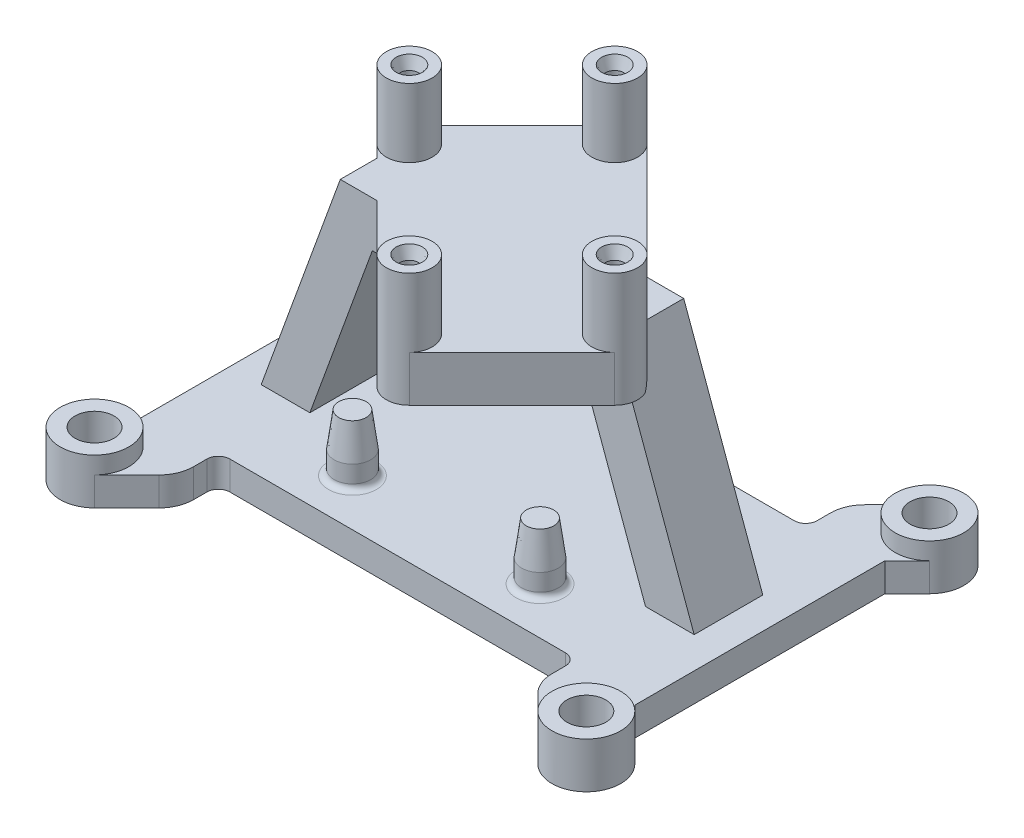
SolidWorks part; units mm, degrees
ref_plane "Front Plane" through (0, 0, 0) normal (0, 0, 1) x (1, 0, 0)
ref_plane "Top Plane" through (0, 0, 0) normal (0, 1, 0) x (1, 0, 0)
ref_plane "Right Plane" through (0, 0, 0) normal (1, 0, 0) x (0, 0, -1)
sketch "Sketch1" plane through (0, 0, 0) normal (0, 1, 0) x (1, 0, 0)
  line L1 (-21.5, 15) -> (21.5, 15) construction
  line L2 (-21.5, 15) -> (-21.5, -15) construction
  line L3 (-21.5, -15) -> (21.5, -15) construction
  line L4 (21.5, 15) -> (21.5, -15) construction
  line L5 (-21.5, 15) -> (21.5, -15) construction
  line L6 (-21.5, -15) -> (21.5, 15) construction
  circle A0 centre (-21.5, 15) radius 1.7
  circle A1 centre (21.5, 15) radius 1.7
  circle A2 centre (21.5, -15) radius 1.7
  circle A3 centre (-21.5, -15) radius 1.7
  circle A4 centre (-21.5, 15) radius 3
  circle A5 centre (-21.5, -15) radius 3
  circle A6 centre (21.5, -15) radius 3
  circle A7 centre (21.5, 15) radius 3
  point P0 (0, 0)
  dimension "D3" = 3.4
  dimension "D4" = 6
  dimension "D1" = 43
  dimension "D2" = 30
extrude "Boss-Extrude1" add sketch "Sketch1" along normal blind 4
sketch "Sketch2" plane through (0, 0, 0) normal (0, 1, 0) x (1, 0, 0)
  line L0 (-21.5, 15) -> (-18.6716, 12.1716) construction
  line L1 (-19.3787, 17.1213) -> (-16.5503, 14.2929)
  line L2 (-23.6213, 12.8787) -> (-21.6716, 10.9289)
  line L3 (-21.5, -15) -> (-18.6716, -12.1716) construction
  line L4 (-23.6213, -12.8787) -> (-21.6716, -10.9289)
  line L5 (-19.3787, -17.1213) -> (-16.5503, -14.2929)
  line L6 (-18.6716, 12.1716) -> (-18.6716, -12.1716) construction
  line L7 (-15.6716, 12.1716) -> (-15.6716, -12.1716)
  line L8 (-21.6716, 10.9289) -> (-21.6716, -10.9289)
  line L9 (0, -1000) -> (0, 49000) construction
  line L10 (18.6716, 12.1716) -> (18.6716, -12.1716) construction
  line L11 (21.5, -15) -> (18.6716, -12.1716) construction
  line L12 (21.5, 15) -> (18.6716, 12.1716) construction
  line L13 (21.6716, 10.9289) -> (21.6716, -10.9289)
  line L14 (15.6716, 12.1716) -> (15.6716, -12.1716)
  line L15 (19.3787, -17.1213) -> (16.5503, -14.2929)
  line L16 (23.6213, -12.8787) -> (21.6716, -10.9289)
  line L17 (23.6213, 12.8787) -> (21.6716, 10.9289)
  line L18 (19.3787, 17.1213) -> (16.5503, 14.2929)
  arc A0 (-19.3787, 17.1213) -> (-23.6213, 12.8787) centre (-21.5, 15) ccw
  circle A2 centre (-21.5, 15) radius 3 construction
  arc A3 (-23.6213, -12.8787) -> (-19.3787, -17.1213) centre (-21.5, -15) ccw
  arc A4 (-16.5503, -14.2929) -> (-15.6716, -12.1716) centre (-18.6716, -12.1716) ccw
  circle A5 centre (-21.5, -15) radius 3 construction
  arc A6 (-15.6716, 12.1716) -> (-16.5503, 14.2929) centre (-18.6716, 12.1716) ccw
  arc A7 (-16.5503, -14.2929) -> (-15.6716, -12.1716) centre (-18.6716, -12.1716) ccw
  arc A8 (-15.6716, 12.1716) -> (-16.5503, 14.2929) centre (-18.6716, 12.1716) ccw
  arc A9 (15.6716, 12.1716) -> (16.5503, 14.2929) centre (18.6716, 12.1716) cw
  arc A10 (16.5503, -14.2929) -> (15.6716, -12.1716) centre (18.6716, -12.1716) cw
  arc A11 (15.6716, 12.1716) -> (16.5503, 14.2929) centre (18.6716, 12.1716) cw
  arc A12 (16.5503, -14.2929) -> (15.6716, -12.1716) centre (18.6716, -12.1716) cw
  arc A13 (23.6213, -12.8787) -> (19.3787, -17.1213) centre (21.5, -15) cw
  arc A14 (19.3787, 17.1213) -> (23.6213, 12.8787) centre (21.5, 15) cw
  point P2 (-20.0858, 13.5858)
  point P13 (-20.0858, -13.5858)
  point P20 (-18.6716, 0)
  point P41 (18.6716, 0)
  point P42 (20.0858, -13.5858)
  point P43 (20.0858, 13.5858)
  dimension "D1" = 45
  dimension "D2" = 45
  dimension "D3" = 4
  dimension "D4" = 4
  dimension "D5" = 3
  dimension "D6" = 3
extrude "Boss-Extrude2" add sketch "Sketch2" along normal blind 2.5 contours L7 A6 L1 A0 L2 L8 L4 A3 L5 A4 | A14 L18 A9 L14 A10 L15 A13 L16 L13 L17 region at (-19.3328, 0, 0) region at (19.3328, 0, 0)
extrude "Cut-Extrude1" cut sketch "Sketch1<2>" against normal through all both and the other way through all contours A3 | A0 | A1 | A2 region at (-21.5, 0, -15) region at (21.5, 0, -15) region at (21.5, 0, 15) region at (-21.5, 0, 15)
sketch "Sketch1<2>" plane through (0, 0, 0) normal (0, 1, 0) x (1, 0, 0) same geometry as "Sketch1"
sketch "Sketch4" plane through (0, 0, 0) normal (0, 1, 0) x (1, 0, 0)
  line L0 (15.6716, 12.1716) -> (15.6716, -12.1716) construction
  line L1 (-15.6716, 10) -> (15.6716, 10)
  line L2 (-15.6716, 10) -> (-15.6716, -10)
  line L3 (-15.6716, -10) -> (15.6716, -10)
  line L4 (15.6716, 10) -> (15.6716, -10)
  line L5 (-15.6716, 10) -> (15.6716, -10) construction
  line L6 (-15.6716, -10) -> (15.6716, 10) construction
  point P0 (0, 0)
  dimension "D1" = 20
extrude "Boss-Extrude3" add sketch "Sketch4" along normal up to surface (2.5 mm away) up to face at (-18.9122, 2.5, 0)
sketch "Sketch5" plane through (0, 2.5, 0) normal (0, 1, 0) x (1, 0, 0)
  line L0 (-1005.1394, -7.5) -> (48994.8606, -7.5) construction
  line L1 (-10.15, 8) -> (10.15, 8) construction
  line L2 (-10.15, 8) -> (-10.15, -8) construction
  line L3 (-10.15, -8) -> (10.15, -8) construction
  line L4 (10.15, 8) -> (10.15, -8) construction
  line L5 (-10.15, 8) -> (10.15, -8) construction
  line L6 (-10.15, -8) -> (10.15, 8) construction
  line L7 (-9.65, -1006.7474) -> (-9.65, 48993.2526) construction
  circle A0 centre (-8.05, -5.9) radius 1.6
  circle A1 centre (8.35, -5.9) radius 1.6
  point P0 (0, 0)
  dimension "D3" = 3.2
  dimension "D6" = 1.8
  dimension "D1" = 16
  dimension "D2" = 20.3
  dimension "D4" = 0.5
  dimension "D5" = 0.5
extrude "Boss-Extrude4" add sketch "Sketch5" along normal blind 5
chamfer "Chamfer1" distance 3 distance2 0.4 2 edges at (8.35, 7.5, 7.5) (-8.05, 7.5, 7.5) first distance on face at (8.35, 7.5, 7.5) first distance on face at (-8.05, 7.5, 7.5)
fillet "Fillet1" radius 0.5 2 edges at (8.35, 2.5, 7.5) (-8.05, 2.5, 7.5)
fillet "Fillet2" radius 1 4 edges at (-15.6716, 1.25, -10) (15.6716, 1.25, -10) (15.6716, 1.25, 10) (-15.6716, 1.25, 10)
sketch "Sketch6" plane through (0, 0, 0) normal (0, 0, 1) x (1, 0, 0)
  line L0 (-14.6716, 2.5) -> (-9.212, 17.5)
  line L1 (-9.212, 17.5) -> (9.212, 17.5)
  line L2 (-201005.1394, 2.5) -> (248994.8606, 2.5) construction
  line L3 (-14.6716, 2.5) -> (-18.9283, 2.5)
  line L4 (-18.9283, 2.5) -> (-12.0128, 21.5)
  line L5 (-12.0128, 21.5) -> (12.0128, 21.5)
  line L6 (-10.15, 2.5) -> (10.15, 2.5) construction
  line L7 (0, -1000) -> (0, 49000) construction
  line L8 (18.9283, 2.5) -> (12.0128, 21.5)
  line L9 (14.6716, 2.5) -> (18.9283, 2.5)
  line L10 (14.6716, 2.5) -> (9.212, 17.5)
  point P18 (0, 21.5)
  point P21 (0, 17.5)
  dimension "D1" = 70
  dimension "D2" = 4
  dimension "D3" = 4
  dimension "D4" = 15
extrude "Boss-Extrude5" add sketch "Sketch6" along normal blind 3 and the other way blind 3
sketch "Sketch9" plane through (0, 2.5, 0) normal (0, 1, 0) x (1, 0, 0)
  line L0 (0, 0) -> (35355.3391, 35355.3391) construction
  line L1 (-2.6941, 15.2664) -> (15.2664, -2.6941) construction
  line L2 (-2.6941, 15.2664) -> (-15.2664, 2.6941) construction
  line L3 (-15.2664, 2.6941) -> (2.6941, -15.2664) construction
  line L4 (15.2664, -2.6941) -> (2.6941, -15.2664) construction
  line L5 (-2.6941, 15.2664) -> (2.6941, -15.2664) construction
  line L6 (-15.2664, 2.6941) -> (15.2664, -2.6941) construction
  line L7 (-2.6941, 11.6743) -> (11.6743, -2.6941) construction
  line L8 (-2.6941, 11.6743) -> (-11.6743, 2.6941) construction
  line L9 (-11.6743, 2.6941) -> (2.6941, -11.6743) construction
  line L10 (11.6743, -2.6941) -> (2.6941, -11.6743) construction
  line L11 (-2.6941, 11.6743) -> (2.6941, -11.6743) construction
  line L12 (-11.6743, 2.6941) -> (11.6743, -2.6941) construction
  line L13 (-1000, 0) -> (49000, 0) construction
  circle A0 centre (-2.6941, 11.6743) radius 0.8
  circle A1 centre (11.6743, -2.6941) radius 0.8
  circle A2 centre (2.6941, -11.6743) radius 0.8
  circle A3 centre (-11.6743, 2.6941) radius 0.8
  circle A4 centre (-2.6941, 11.6743) radius 2
  circle A5 centre (-11.6743, 2.6941) radius 2
  circle A6 centre (11.6743, -2.6941) radius 2
  circle A7 centre (2.6941, -11.6743) radius 2
  point P3 (0, 0)
  point P8 (0, 0)
  dimension "D5" = 1.6
  dimension "D6" = 4
  dimension "D1" = 17.78
  dimension "D2" = 25.4
  dimension "D3" = 12.7
  dimension "D4" = 20.32
  dimension "D7" = 45
extrude "Boss-Extrude10" add sketch "Sketch9" along normal blind 10 from surface starting at face at (0, 17.5, 0)
sketch "Sketch13" plane through (0, 17.5, 0) normal (0, -1, 0) x (1, 0, 0)
  line L0 (-13.0885, -4.1083) -> (-4.1083, -13.0885)
  line L1 (-1.2799, -13.0885) -> (13.0885, 1.2799)
  line L2 (1.2799, 13.0885) -> (-13.0885, -1.2799)
  line L3 (4.1083, 13.0885) -> (13.0885, 4.1083)
  circle A0 centre (-2.6941, -11.6743) radius 2 construction
  circle A1 centre (11.6743, 2.6941) radius 2 construction
  circle A2 centre (2.6941, 11.6743) radius 2 construction
  circle A3 centre (-11.6743, -2.6941) radius 2 construction
  arc A4 (-4.1083, -13.0885) -> (-1.2799, -13.0885) centre (-2.6941, -11.6743) ccw
  arc A5 (13.0885, 1.2799) -> (13.0885, 4.1083) centre (11.6743, 2.6941) ccw
  arc A6 (4.1083, 13.0885) -> (1.2799, 13.0885) centre (2.6941, 11.6743) ccw
  arc A7 (-13.0885, -1.2799) -> (-13.0885, -4.1083) centre (-11.6743, -2.6941) ccw
  point P20 (0, 0)
  point P21 (0, 0)
  point P22 (0, 0)
  point P23 (0, 0)
  point P24 (0, 0)
extrude "Boss-Extrude11" add sketch "Sketch13" against normal blind 4
chamfer "Chamfer2" distance 1 angle 19 4 edges at (2.6941, 27.5, 10.8743) (11.6743, 27.5, 1.8941) (-2.6941, 27.5, -12.4743) (-11.6743, 27.5, -3.4941) first distance on face at (2.6941, 21.5, 12.4743) first distance on face at (11.6743, 27.5, 1.8941) first distance on face at (-2.6941, 21.5, -10.8743) first distance on face at (-11.6743, 27.5, -3.4941)
